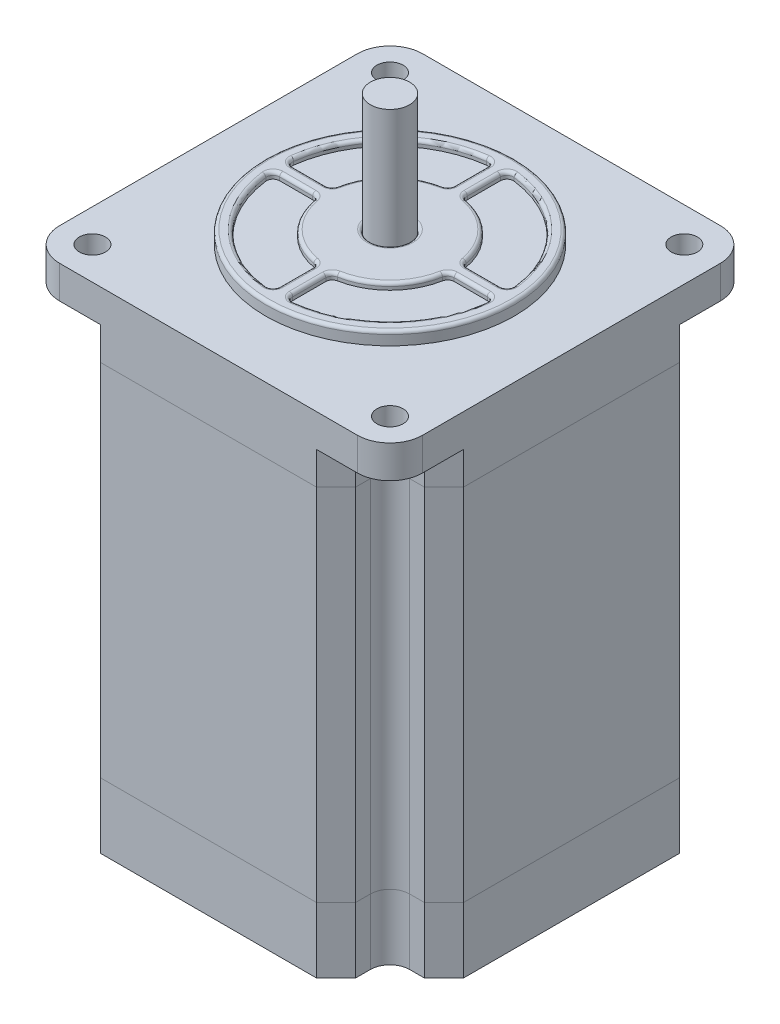
SolidWorks part; units mm, degrees
ref_plane "Front Plane" through (0, 0, 0) normal (0, 0, 1) x (1, 0, 0)
ref_plane "Top Plane" through (0, 0, 0) normal (0, 1, 0) x (1, 0, 0)
ref_plane "Right Plane" through (0, 0, 0) normal (1, 0, 0) x (0, 0, -1)
sketch "Sketch1" plane through (0, 0, 0) normal (0, 1, 0) x (1, 0, 0)
  line L0 (0, 44.25) -> (3, 47.25)
  line L1 (11.25, 0) -> (44.25, 0)
  line L2 (0, 11.25) -> (0, 44.25)
  line L3 (11.25, 55.5) -> (44.25, 55.5)
  line L4 (55.5, 11.25) -> (55.5, 44.25)
  line L5 (0, 11.25) -> (3, 8.25)
  line L6 (44.25, 55.5) -> (47.25, 52.5)
  line L7 (44.25, 0) -> (47.25, 3)
  line L8 (5.25, 47.25) -> (3, 47.25)
  line L9 (8.25, 52.5) -> (11.25, 55.5)
  line L10 (47.25, 3) -> (47.25, 5.25)
  line L11 (52.5, 47.25) -> (55.5, 44.25)
  line L12 (52.5, 8.25) -> (55.5, 11.25)
  line L13 (8.25, 3) -> (11.25, 0)
  line L15 (8.25, 52.5) -> (8.25, 50.25)
  line L24 (50.25, 8.25) -> (52.5, 8.25)
  line L27 (50.25, 47.25) -> (52.5, 47.25)
  line L30 (47.25, 52.5) -> (47.25, 50.25)
  line L31 (3, 8.25) -> (5.25, 8.25)
  line L32 (8.25, 5.25) -> (8.25, 3)
  arc A0 (5.25, 47.25) -> (8.25, 50.25) centre (5.25, 50.25) ccw
  arc A1 (50.25, 47.25) -> (47.25, 50.25) centre (50.25, 50.25) cw
  arc A2 (47.25, 5.25) -> (50.25, 8.25) centre (50.25, 5.25) cw
  arc A3 (5.25, 8.25) -> (8.25, 5.25) centre (5.25, 5.25) cw
  circle A4 centre (27.75, 27.75) radius 3
  point P0 (0, 0)
  point P1 (55.5, 55.5)
  point P2 (0, 55.5)
  point P3 (55.5, 0)
  dimension "D3" = 3
  dimension "D4" = 3
  dimension "D1" = 55.5
  dimension "D2" = 55.5
extrude "Boss-Extrude1" add sketch "Sketch1" along normal blind 10
ref_plane "Plane1" through (0, 10, 0) normal (0, 1, 0) x (1, 0, 0)
sketch "Sketch2" plane through (0, 10, 0) normal (0, 1, 0) x (1, 0, 0)
  line L0 (0, 44.25) -> (0, 11.25)
  line L1 (0, 11.25) -> (3, 8.25)
  line L2 (3, 8.25) -> (5.25, 8.25)
  line L3 (0, 44.25) -> (3, 47.25)
  line L4 (3, 47.25) -> (5.25, 47.25)
  line L5 (8.25, 50.25) -> (8.25, 52.5)
  line L6 (8.25, 52.5) -> (11.25, 55.5)
  line L7 (11.25, 55.5) -> (8.25, 52.5) construction
  line L8 (11.25, 55.5) -> (44.25, 55.5)
  line L9 (44.25, 55.5) -> (11.25, 55.5) construction
  line L10 (44.25, 55.5) -> (47.25, 52.5)
  line L11 (47.25, 52.5) -> (47.25, 50.25)
  line L12 (50.25, 47.25) -> (52.5, 47.25)
  line L13 (52.5, 47.25) -> (50.25, 47.25) construction
  line L14 (52.5, 47.25) -> (55.5, 44.25)
  line L15 (55.5, 44.25) -> (55.5, 11.25)
  line L16 (55.5, 11.25) -> (55.5, 44.25) construction
  line L17 (55.5, 11.25) -> (52.5, 8.25)
  line L18 (52.5, 8.25) -> (50.25, 8.25)
  line L19 (47.25, 5.25) -> (47.25, 3)
  line L20 (47.25, 3) -> (44.25, 0)
  line L21 (44.25, 0) -> (11.25, 0)
  line L22 (11.25, 0) -> (8.25, 3)
  line L23 (8.25, 3) -> (8.25, 5.25)
  arc A0 (8.25, 50.25) -> (5.25, 47.25) centre (5.25, 50.25) cw
  arc A1 (8.25, 5.25) -> (5.25, 8.25) centre (5.25, 5.25) ccw construction
  arc A2 (8.25, 5.25) -> (5.25, 8.25) centre (5.25, 5.25) ccw
  arc A3 (47.25, 50.25) -> (50.25, 47.25) centre (50.25, 50.25) ccw
  arc A4 (50.25, 8.25) -> (47.25, 5.25) centre (50.25, 5.25) ccw
  circle A5 centre (27.75, 27.75) radius 3
extrude "Boss-Extrude2" add sketch "Sketch2" along normal blind 55 separate body
ref_plane "Plane2" through (0, 65, 0) normal (0, 1, 0) x (1, 0, 0)
sketch "Sketch3" plane through (0, 65, 0) normal (0, 1, 0) x (1, 0, 0)
  line L0 (0, 44.25) -> (3, 47.25)
  line L1 (3, 47.25) -> (5.25, 47.25)
  line L2 (8.25, 50.25) -> (8.25, 52.5)
  line L3 (8.25, 52.5) -> (11.25, 55.5)
  line L4 (11.25, 55.5) -> (44.25, 55.5)
  line L5 (44.25, 55.5) -> (11.25, 55.5) construction
  line L6 (44.25, 55.5) -> (47.25, 52.5)
  line L7 (47.25, 52.5) -> (47.25, 50.25)
  line L8 (50.25, 47.25) -> (52.5, 47.25)
  line L9 (52.5, 47.25) -> (55.5, 44.25)
  line L10 (55.5, 44.25) -> (55.5, 11.25)
  line L11 (55.5, 11.25) -> (52.5, 8.25)
  line L12 (52.5, 8.25) -> (50.25, 8.25)
  line L13 (47.25, 5.25) -> (47.25, 3)
  line L14 (47.25, 3) -> (44.25, 0)
  line L15 (44.25, 0) -> (11.25, 0)
  line L16 (11.25, 0) -> (44.25, 0) construction
  line L17 (11.25, 0) -> (8.25, 3)
  line L18 (8.25, 5.25) -> (8.25, 3) construction
  line L19 (8.25, 3) -> (8.25, 5.25)
  line L20 (0, 44.25) -> (0, 11.25)
  line L21 (0, 11.25) -> (3, 8.25)
  line L22 (3, 8.25) -> (5.25, 8.25)
  line L23 (3, 8.25) -> (5.25, 8.25) construction
  arc A0 (47.25, 50.25) -> (50.25, 47.25) centre (50.25, 50.25) ccw
  arc A1 (50.25, 8.25) -> (47.25, 5.25) centre (50.25, 5.25) ccw
  arc A2 (5.25, 8.25) -> (8.25, 5.25) centre (5.25, 5.25) cw
  arc A3 (5.25, 47.25) -> (8.25, 50.25) centre (5.25, 50.25) ccw
  circle A4 centre (27.75, 27.75) radius 3
extrude "Boss-Extrude3" add sketch "Sketch3" along normal blind 10 separate body
ref_plane "Plane3" through (0, 75, 0) normal (0, 1, 0) x (1, 0, 0)
sketch "Sketch4" plane through (0, 75, 0) normal (0, 1, 0) x (1, 0, 0)
  line L1 (5, 0) -> (50.5, 0)
  line L2 (0, 5) -> (0, 50.5)
  line L3 (5, 55.5) -> (50.5, 55.5)
  line L4 (55.5, 5) -> (55.5, 50.5)
  arc A0 (50.5, 0) -> (55.5, 5) centre (50.5, 5) ccw
  arc A1 (5, 0) -> (0, 5) centre (5, 5) cw
  arc A2 (50.5, 55.5) -> (55.5, 50.5) centre (50.5, 50.5) cw
  arc A3 (0, 50.5) -> (5, 55.5) centre (5, 50.5) cw
  dimension "D3" = 5
extrude "Boss-Extrude4" add sketch "Sketch4" against normal blind 5
sketch "Sketch5" plane through (0, 75, 0) normal (0, 1, 0) x (1, 0, 0)
  circle A0 centre (5, 50.5) radius 2
  circle A1 centre (50.25, 50.25) radius 2
  circle A2 centre (5, 5) radius 2
  circle A3 centre (50.5, 5) radius 2
  circle A4 centre (27.75, 27.75) radius 3
extrude "Cut-Extrude1" cut sketch "Sketch5" against normal blind 5
ref_plane "Plane5" through (0, 75, 0) normal (0, 1, 0) x (1, 0, 0)
sketch "Sketch8" plane through (0, 75, 0) normal (0, 1, 0) x (1, 0, 0)
  line L1 (38.5667, 28.75) -> (43.6245, 28.75)
  line L2 (11.8755, 28.75) -> (16.9333, 28.75)
  line L3 (26.75, 16.9333) -> (26.75, 11.8755)
  line L4 (26.75, 43.6245) -> (26.75, 38.5667)
  line L6 (28.75, 43.6245) -> (28.75, 38.5667)
  line L7 (28.75, 16.9333) -> (28.75, 11.8755)
  line L8 (11.8755, 26.75) -> (16.9333, 26.75)
  line L9 (38.5667, 26.75) -> (43.6245, 26.75)
  circle A0 centre (27.75, 27.75) radius 19
  arc A1 (25.625, 44.6167) -> (10.8833, 29.875) centre (27.75, 27.75) ccw
  arc A2 (25.9318, 37.5833) -> (17.9167, 29.5682) centre (27.75, 27.75) ccw
  arc A3 (29.5682, 17.9167) -> (37.5833, 25.9318) centre (27.75, 27.75) ccw
  arc A4 (29.875, 10.8833) -> (44.6167, 25.625) centre (27.75, 27.75) ccw
  arc A5 (10.8833, 25.625) -> (25.625, 10.8833) centre (27.75, 27.75) ccw
  arc A6 (17.9167, 25.9318) -> (25.9318, 17.9167) centre (27.75, 27.75) ccw
  arc A7 (37.5833, 29.5682) -> (29.5682, 37.5833) centre (27.75, 27.75) ccw
  arc A8 (44.6167, 29.875) -> (29.875, 44.6167) centre (27.75, 27.75) ccw
  arc A9 (11.8755, 26.75) -> (10.8833, 25.625) centre (11.8755, 25.75) ccw
  arc A10 (17.9167, 25.9318) -> (16.9333, 26.75) centre (16.9333, 25.75) ccw
  arc A11 (26.75, 11.8755) -> (25.625, 10.8833) centre (25.75, 11.8755) cw
  arc A12 (25.9318, 17.9167) -> (26.75, 16.9333) centre (25.75, 16.9333) cw
  arc A13 (29.5682, 17.9167) -> (28.75, 16.9333) centre (29.75, 16.9333) ccw
  arc A14 (28.75, 11.8755) -> (29.875, 10.8833) centre (29.75, 11.8755) ccw
  arc A15 (44.6167, 25.625) -> (43.6245, 26.75) centre (43.6245, 25.75) ccw
  arc A16 (38.5667, 26.75) -> (37.5833, 25.9318) centre (38.5667, 25.75) ccw
  arc A17 (38.5667, 28.75) -> (37.5833, 29.5682) centre (38.5667, 29.75) cw
  arc A18 (44.6167, 29.875) -> (43.6245, 28.75) centre (43.6245, 29.75) cw
  arc A19 (29.875, 44.6167) -> (28.75, 43.6245) centre (29.75, 43.6245) ccw
  arc A20 (28.75, 38.5667) -> (29.5682, 37.5833) centre (29.75, 38.5667) ccw
  arc A21 (26.75, 38.5667) -> (25.9318, 37.5833) centre (25.75, 38.5667) cw
  arc A22 (26.75, 43.6245) -> (25.625, 44.6167) centre (25.75, 43.6245) ccw
  arc A23 (10.8833, 29.875) -> (11.8755, 28.75) centre (11.8755, 29.75) ccw
  arc A24 (17.9167, 29.5682) -> (16.9333, 28.75) centre (16.9333, 29.75) cw
  point P11 (13.8274, 27.75)
  dimension "D1" = 38
extrude "Boss-Extrude5" add sketch "Sketch8" along normal blind 2
sketch "Sketch9" plane through (0, 77, 0) normal (0, 1, 0) x (1, 0, 0)
  circle A0 centre (27.75, 27.75) radius 3
extrude "Cut-Extrude2" cut sketch "Sketch9" against normal blind 2 and the other way blind 2
fillet "Fillet1" radius 0.5 34 edges at (26.4114, 77, -44.3745) (15.7292, 77, -39.7708) (11.1255, 77, -29.0886) (14.4044, 77, -28.75) (17.5729, 77, -28.9813) (20.6789, 77, -34.8211) (26.5187, 77, -37.9271) (26.75, 77, -41.0956) (29.0886, 77, -11.1255) (39.7708, 77, -15.7292) (44.3745, 77, -26.4114) (41.0956, 77, -26.75) (37.9271, 77, -26.5187) (34.8211, 77, -20.6789) (28.9813, 77, -17.5729) (28.75, 77, -14.4044) (27.75, 77, -8.75) (26.4114, 77, -11.1255) (26.75, 77, -14.4044) (26.5187, 77, -17.5729) (20.6789, 77, -20.6789) (17.5729, 77, -26.5187) (14.4044, 77, -26.75) (11.1255, 77, -26.4114) (15.7292, 77, -15.7292) (44.3745, 77, -29.0886) (39.7708, 77, -39.7708) (29.0886, 77, -44.3745) (28.75, 77, -41.0956) (28.9813, 77, -37.9271) (34.8211, 77, -34.8211) (37.9271, 77, -28.9813) (41.0956, 77, -28.75) (27.75, 77, -24.75)
sketch "Sketch10" plane through (0, 75, 0) normal (0, 1, 0) x (1, 0, 0)
  circle A0 centre (27.75, 27.75) radius 19
extrude "Boss-Extrude6" add sketch "Sketch10" along normal blind 1
sketch "Sketch11" plane through (0, 76, 0) normal (0, 1, 0) x (1, 0, 0)
  circle A0 centre (27.75, 27.75) radius 3
extrude "Cut-Extrude3" cut sketch "Sketch11" against normal blind 11
ref_plane "Plane6" through (0, -10, 0) normal (0, -1, 0) x (-1, 0, 0)
sketch "Sketch12" plane through (0, -10, 0) normal (0, -1, 0) x (-1, 0, 0)
  circle A0 centre (-27.75, 27.75) radius 3
extrude "Boss-Extrude7" add sketch "Sketch12" against normal blind 105 separate body
